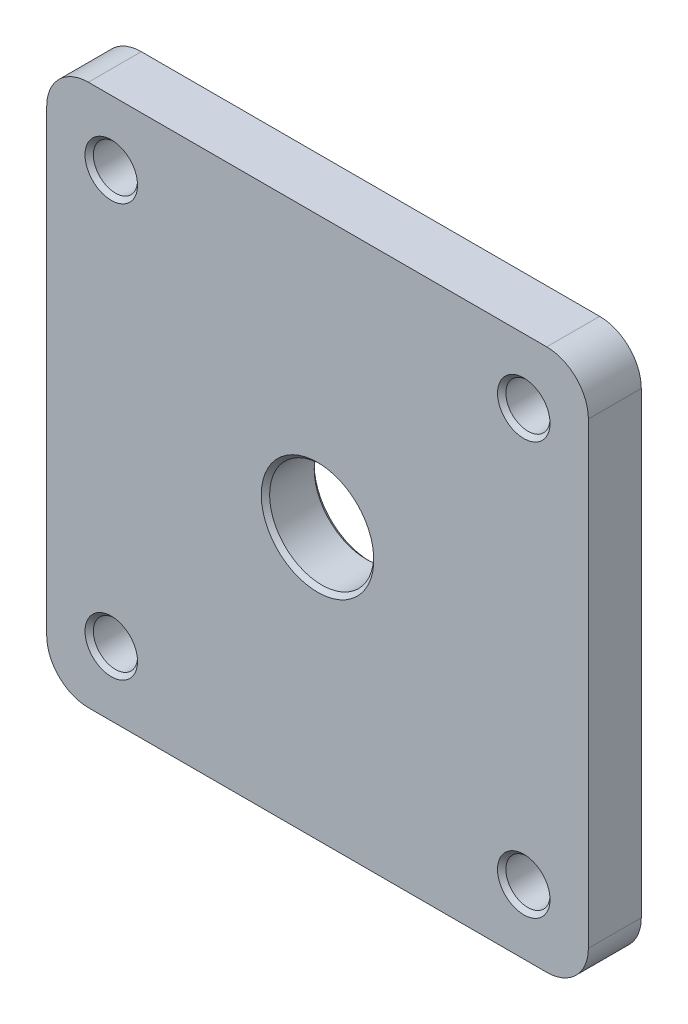
SolidWorks part; units mm, degrees
material "6061 Alloy"
ref_plane "Front Plane" through (0, 0, 0) normal (0, 0, 1) x (1, 0, 0)
ref_plane "Top Plane" through (0, 0, 0) normal (0, 1, 0) x (1, 0, 0)
ref_plane "Right Plane" through (0, 0, 0) normal (1, 0, 0) x (0, 0, -1)
sketch "Sketch1" plane through (0, 0, 0) normal (0, 0, 1) x (1, 0, 0)
  line L1 (-32.5, -32.5) -> (32.5, -32.5)
  line L2 (-32.5, -32.5) -> (-32.5, 32.5)
  line L3 (-32.5, 32.5) -> (32.5, 32.5)
  line L4 (32.5, -32.5) -> (32.5, 32.5)
  line L5 (-32.5, -32.5) -> (32.5, 32.5) construction
  line L6 (-32.5, 32.5) -> (32.5, -32.5) construction
  point P0 (0, 0)
  dimension "D1" = 65
extrude "1/4 in Sheet Metal" add sketch "Sketch1" along normal mid plane 6.35
hole_wizard "M12 Clearance Hole" positions "Sketch3" profile "Sketch4" hole size "M12" standard "ANSI Metric" end condition up to next
sketch "Sketch3" plane through (0, 0, 3.175) normal (0, 0, 1) x (1, 0, 0)
  point P0 (0, 0)
sketch "Sketch4" plane through (0, 0, 3.175) normal (1, 0, 0) x (0, -1, 0)
  line L0 (0, 0) -> (0, 6.35)
  line L1 (0, 6.35) -> (6.25, 6.35)
  line L2 (6.25, 6.35) -> (6.25, 0)
  line L5 (6.25, 0) -> (0, 0)
  line L11 (0, -6.35) -> (0, 107.95) construction
  dimension "Thru Hole Dia." = 12.5
  dimension "Thru Hole Depth" = 6.35
hole_wizard "M5 Clearance Hole1" positions "Sketch5" profile "Sketch6" hole size "M5" standard "ANSI Metric" end condition up to next
sketch "Sketch5" plane through (0, 0, 3.175) normal (0, 0, 1) x (1, 0, 0)
  line L0 (0, 0) -> (35, 0) construction
  line L2 (0, 0) -> (24.7487, 24.7487) construction
  line L4 (0, 0) -> (-24.7487, -24.7487) construction
  line L6 (-24.7487, 24.7487) -> (24.7487, -24.7487) construction
  circle A0 centre (0, 0) radius 35 construction
  point P0 (24.7487, 24.7487)
  point P2 (-24.7487, 24.7487)
  point P4 (-24.7487, -24.7487)
  point P6 (24.7487, -24.7487)
  dimension "D1" = 70
  dimension "D2" = 45
sketch "Sketch6" plane through (24.7487, 24.7487, 3.175) normal (1, 0, 0) x (0, -1, 0)
  line L0 (0, 0) -> (0, 6.35)
  line L1 (0, 6.35) -> (2.65, 6.35)
  line L2 (2.65, 6.35) -> (2.65, 0)
  line L5 (2.65, 0) -> (0, 0)
  line L11 (0, -6.35) -> (0, 107.95) construction
  dimension "Thru Hole Dia." = 5.3
  dimension "Thru Hole Depth" = 6.35
fillet "Fillet1 5 mm" radius 5 4 edges at (-32.5, -32.5, 0) (-32.5, 32.5, 0) (32.5, -32.5, 0) (32.5, 32.5, 0)
chamfer "Chamfer 0.5 mm" distance 0.5 angle 45 10 edges at (-27.3987, -24.7487, -3.175) (-22.0987, -24.7487, 3.175) (22.0987, -24.7487, -3.175) (27.3987, -24.7487, 3.175) (22.0987, 24.7487, -3.175) (27.3987, 24.7487, 3.175) (-27.3987, 24.7487, -3.175) (-22.0987, 24.7487, 3.175) (-6.25, 0, -3.175) (6.25, 0, 3.175)
